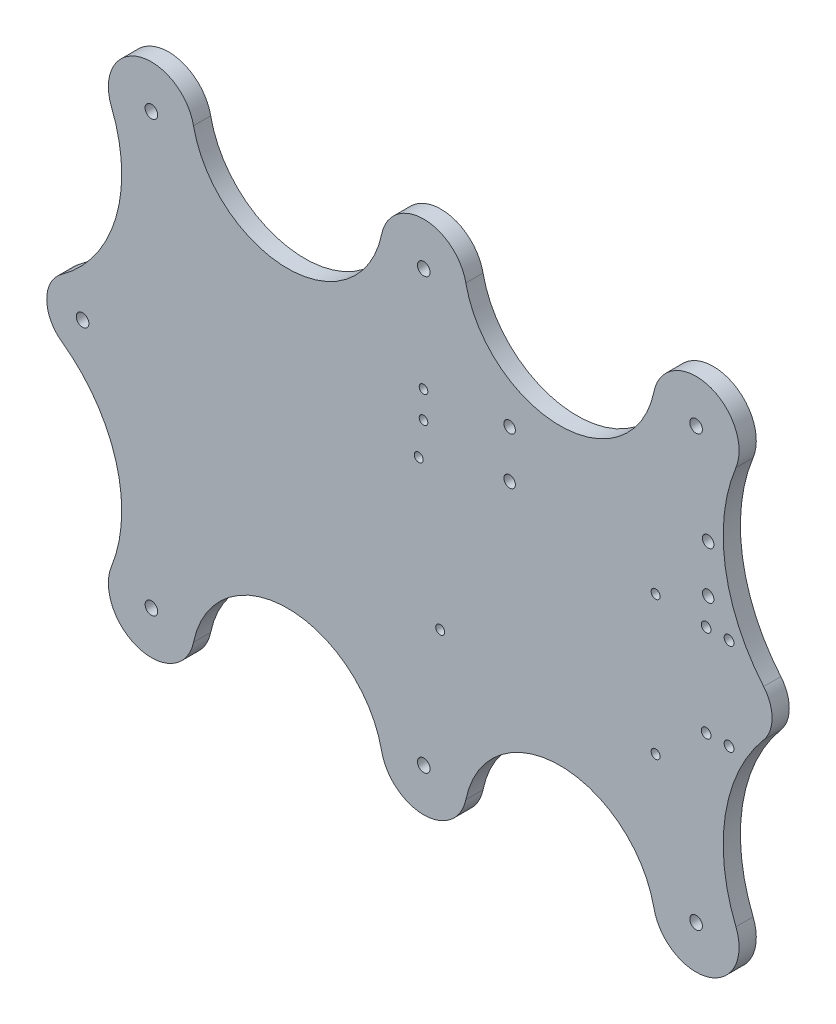
SolidWorks part; units mm, degrees
material "ABS"
ref_plane "Front Plane" through (0, 0, 0) normal (0, 0, 1) x (1, 0, 0)
ref_plane "Top Plane" through (0, 0, 0) normal (0, 1, 0) x (1, 0, 0)
ref_plane "Right Plane" through (0, 0, 0) normal (1, 0, 0) x (0, 0, -1)
sketch "Sketch2" plane through (0, 0, 0) normal (0, 0, 1) x (1, 0, 0)
  line L1 (-235.4178, -26.2985) -> (17.5822, -26.2985) construction
  arc A0 (14.6436, -34.3502) -> (14.6436, -18.2467) centre (5.0822, -26.2985) ccw construction
  arc A1 (14.6436, -34.3502) -> (14.6436, -18.2467) centre (5.0822, -26.2985) ccw
  arc A2 (14.6436, -34.3502) -> (4.9734, -95.6385) centre (60.5381, -72.9986) ccw
  arc A3 (14.6436, -34.3502) -> (0.5381, -72.9986) centre (60.5381, -72.9986) ccw construction
  arc A5 (-23.6085, -104.3288) -> (-89.2271, -104.3288) centre (-56.4178, -111.0964) ccw
  arc A7 (-118.6085, -104.3288) -> (-184.2271, -104.3288) centre (-151.4178, -111.0964) ccw
  arc A9 (-212.8436, -95.7244) -> (-230.1869, -36.4676) centre (-259.2631, -77.144) ccw
  arc A10 (-230.1869, -16.1294) -> (-230.1869, -36.4676) centre (-222.9178, -26.2985) ccw
  arc A11 (-212.8436, -95.7244) -> (-184.2271, -104.3288) centre (-198.9178, -101.2985) ccw
  arc A12 (-118.6085, -104.3288) -> (-89.2271, -104.3288) centre (-103.9178, -101.2985) ccw
  arc A13 (-23.6085, -104.3288) -> (4.9734, -95.6385) centre (-8.9178, -101.2985) ccw
  arc A14 (-23.6085, 51.7318) -> (4.9734, 43.0415) centre (-8.9178, 48.7015) cw
  arc A15 (-118.6085, 51.7318) -> (-89.2271, 51.7318) centre (-103.9178, 48.7015) cw
  arc A16 (-212.8436, 43.1274) -> (-184.2271, 51.7318) centre (-198.9178, 48.7015) cw
  arc A17 (-212.8436, 43.1274) -> (-230.1869, -16.1294) centre (-259.2631, 24.547) cw
  arc A18 (-118.6085, 51.7318) -> (-184.2271, 51.7318) centre (-151.4178, 58.4995) cw
  arc A19 (-23.6085, 51.7318) -> (-89.2271, 51.7318) centre (-56.4178, 58.4995) cw
  arc A20 (14.6436, -18.2467) -> (4.9734, 43.0415) centre (60.5381, 20.4016) cw
extrude "Boss-Extrude1" add sketch "Sketch2" along normal blind 6 contours A1 A20 A14 A19 A15 A18 A16 A17 A10 A9 A11 A7 A12 A5 A13 A2
sketch "Sketch3" plane through (0, 0, 6) normal (0, 0, 1) x (1, 0, 0)
  circle A0 centre (-222.9178, -26.2985) radius 2.2
  circle A1 centre (-198.9178, -101.2985) radius 2.2
  circle A2 centre (-103.9178, -101.2985) radius 2.2
  circle A3 centre (-8.9178, -101.2985) radius 2.2
  circle A8 centre (-5.4178, -10.2985) radius 1.7
  circle A9 centre (-5.4178, -42.2985) radius 1.7
  circle A10 centre (2.5822, -42.2985) radius 1.7
  circle A11 centre (2.5822, -10.2985) radius 1.7
  circle A12 centre (-8.9178, 48.7015) radius 2.2
  arc A13 (-6.7178, 48.7015) -> (-11.1178, 48.7015) centre (-8.9178, 48.7015) ccw construction
  circle A14 centre (-103.9178, 48.7015) radius 2.2
  circle A15 centre (-198.9178, 48.7015) radius 2.2
extrude "Cut-Extrude1" cut sketch "Sketch3" against normal through all
ref_plane "Plane1" through (0, -26.2985, 0) normal (0, 1, 0) x (1, 0, 0)
ref_plane "Plane2" through (-103.9178, 0, 0) normal (1, 0, 0) x (0, 0, -1)
sketch "Sketch5" plane through (0, 0, 6) normal (0, 0, 1) x (1, 0, 0)
  circle A0 centre (-89.6279, 15.9096) radius 2
  circle A1 centre (-89.6279, -0.5904) radius 2
  circle A2 centre (-20.3779, -0.5904) radius 2
  circle A3 centre (-20.3779, 15.9096) radius 2
sketch "Sketch6" plane through (0, 0, 6) normal (0, 0, 1) x (1, 0, 0)
  circle A0 centre (-33.0402, -57.4666) radius 1.5621
  circle A1 centre (-108.1734, -57.4666) radius 1.5621
  circle A2 centre (-115.6664, -9.1304) radius 1.5621
  circle A3 centre (-33.0402, -9.1304) radius 1.5621
sketch "Sketch7" plane through (0, 0, 6) normal (0, 0, 1) x (1, 0, 0)
  circle A0 centre (-13.6788, 7.7419) radius 1.5
  circle A1 centre (-13.6788, -1.6227) radius 1.5
sketch "Sketch8" plane through (0, 0, 6) normal (0, 0, 1) x (1, 0, 0)
  circle A0 centre (-47.8075, 15.9096) radius 2
  circle A1 centre (-47.8075, -0.5904) radius 2
  circle A2 centre (-117.0575, -0.5904) radius 2
  circle A3 centre (-117.0575, 15.9096) radius 2
sketch "Sketch9" plane through (0, 0, 6) normal (0, 0, 1) x (1, 0, 0)
  circle A0 centre (-103.995, 12.2819) radius 1.5
  circle A1 centre (-103.995, 2.9173) radius 1.5
  circle A2 centre (-103.9178, 48.7015) radius 2.2 construction
  point P6 (0, 0)
  dimension "D1" = 36.4196
  dimension "D2" = 45.7842
extrude "Cut-Extrude7" cut sketch "Sketch9" against normal through all
sketch "Sketch10" plane through (0, 0, 6) normal (0, 0, 1) x (1, 0, 0)
  circle A0 centre (-4.7026, 15.9096) radius 2
  circle A1 centre (-4.7026, -0.5904) radius 2
  circle A2 centre (-73.9526, 15.9096) radius 2
  circle A3 centre (-73.9526, -0.5904) radius 2
extrude "Cut-Extrude8" cut sketch "Sketch10" against normal through all
sketch "Sketch11" plane through (0, 0, 6) normal (0, 0, 1) x (1, 0, 0)
  circle A0 centre (-23.0402, -9.1304) radius 1.5621
  circle A1 centre (-23.0402, -57.4666) radius 1.5621
  circle A2 centre (-105.6664, -9.1304) radius 1.5621
  circle A3 centre (-98.1734, -57.4666) radius 1.5621
extrude "Cut-Extrude9" cut sketch "Sketch11" against normal through all
